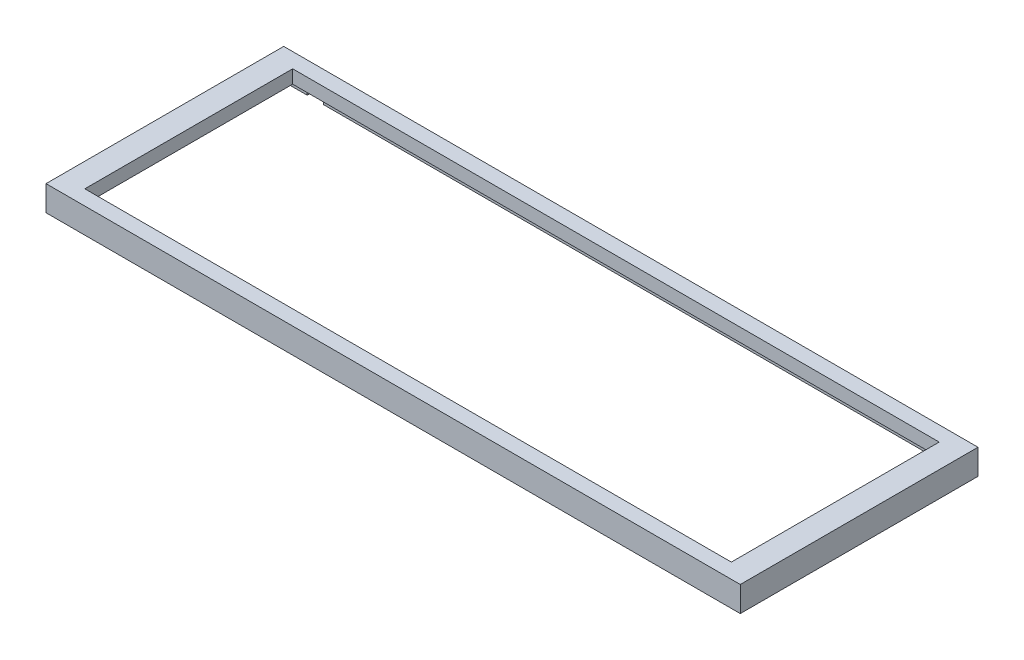
SolidWorks part; units mm, degrees
ref_plane "Front Plane" through (0, 0, 0) normal (0, 0, 1) x (1, 0, 0)
ref_plane "Top Plane" through (0, 0, 0) normal (0, 1, 0) x (1, 0, 0)
ref_plane "Right Plane" through (0, 0, 0) normal (1, 0, 0) x (0, 0, -1)
sketch "Sketch1" plane through (0, 0, 0) normal (0, 1, 0) x (1, 0, 0)
  line L1 (0, 0) -> (363.9, 0)
  line L2 (0, 0) -> (0, 117)
  line L3 (0, 117) -> (363.9, 117)
  line L4 (363.9, 0) -> (363.9, 117)
  line L5 (-13.44, 125.4) -> (377.34, 125.4)
  line L6 (-13.44, 125.4) -> (-13.44, -8.4)
  line L7 (-13.44, -8.4) -> (377.34, -8.4)
  line L8 (377.34, 125.4) -> (377.34, -8.4)
  dimension "D1" = 363.9
  dimension "D2" = 117
  dimension "D3" = 8.4
  dimension "D4" = 13.44
  dimension "D5" = 13.44
  dimension "D6" = 8.4
extrude "Boss-Extrude1" add sketch "Sketch1" along normal blind 7.5
sketch "Sketch2" plane through (0, 0, 0) normal (0, 1, 0) x (1, 0, 0)
  line L0 (-13.44, 125.4) -> (-13.44, -8.4) construction
  line L1 (-8.04, 122.4) -> (371.96, 122.4)
  line L2 (-8.04, 122.4) -> (-8.04, -6)
  line L3 (-8.04, -6) -> (371.96, -6)
  line L4 (371.96, 122.4) -> (371.96, -6)
  line L5 (377.34, 125.4) -> (-13.44, 125.4) construction
  point P6 (-13.44, 58.5)
  line M13 (-13.44, -8.4) -> (-13.44, 125.4)
  line M14 (-13.44, 125.4) -> (377.34, 125.4)
  line M15 (377.34, 125.4) -> (377.34, -8.4)
  line M16 (377.34, -8.4) -> (-13.44, -8.4)
  dimension "D1" = 380
  dimension "D2" = 128.4
  dimension "D3" = 5.4
  dimension "D4" = 3
extrude "Boss-Extrude2" add sketch "Sketch2" against normal blind 6.7 contours L4 L1 L2 L3 M16 M13 M14 M15 region at (-9.3095, 0, -58.5)
sketch "Sketch4" plane through (0, 0, -125.4) normal (0, 0, -1) x (-1, 0, 0)
  line L0 (13.44, -6.7) -> (-377.34, -6.7) construction
  line L1 (-11.96, -6.7) -> (-2.76, -6.7)
  line L2 (-11.96, -6.7) -> (-11.96, -1.7)
  line L3 (-11.96, -1.7) -> (-2.76, -1.7)
  line L4 (-2.76, -6.7) -> (-2.76, -1.7)
  line L6 (13.44, 7.5) -> (13.44, -6.7) construction
  dimension "D1" = 25.4
  dimension "D2" = 9.2
  dimension "D3" = 5
extrude "Cut-Extrude1" cut sketch "Sketch4" against normal blind 7.5
